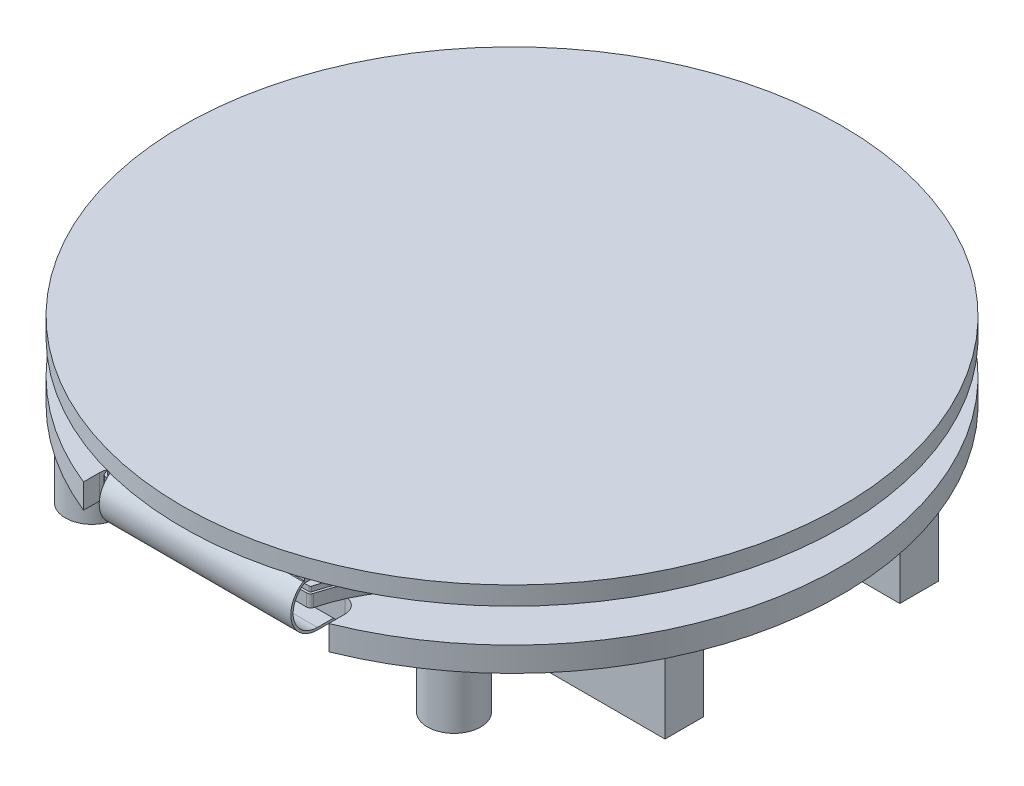
SolidWorks part; units mm, degrees
ref_plane "Front Plane" through (0, 0, 0) normal (0, 0, 1) x (1, 0, 0)
ref_plane "Top Plane" through (0, 0, 0) normal (0, 1, 0) x (1, 0, 0)
ref_plane "Right Plane" through (0, 0, 0) normal (1, 0, 0) x (0, 0, -1)
sketch "Sketch1" plane through (0, 0, 0) normal (0, 1, 0) x (1, 0, 0)
  line L0 (0, 17.75) -> (0, -19.95) construction
  line L1 (-6.75, -19.95) -> (6.75, -19.95)
  circle A0 centre (0, 0) radius 17.75
  arc A1 (-6.75, -19.95) -> (-10.0986, -14.5973) centre (-16.4685, -22.306) ccw
  arc A2 (6.75, -19.95) -> (10.0986, -14.5973) centre (16.4685, -22.306) cw
  point P8 (0, -19.95)
  dimension "D1" = 35.5
  dimension "D4" = 10
  dimension "D2" = 37.7
  dimension "D3" = 13.5
extrude "Boss-Extrude1" add sketch "Sketch1" along normal blind 0.8 contours A0 L0 L1 A2 | L0 A0 A1 L1 | L0 A0 | A0 L0 region at (7.5333, 0, 0) region at (-7.5333, 0, 0) region at (4.3011, 0, 18.3367) region at (-4.3011, 0, 18.3367)
fillet "Fillet1" radius 0.25 2 edges at (6.75, 0.4, 19.95) (-6.75, 0.4, 19.95)
sketch "Sketch2" plane through (0, 0.8, 0) normal (0, 1, 0) x (1, 0, 0)
  line L1 (-6.5553, -19.8) -> (6.5553, -19.8)
  line L3 (-6.5553, -19.95) -> (6.5553, -19.95)
  line L4 (-6.5553, -19.95) -> (6.5553, -19.95) construction
  arc A3 (6.5553, -19.8) -> (6.652, -19.7254) centre (6.5553, -19.7) ccw
  arc A4 (10.0081, -14.4775) -> (6.652, -19.7254) centre (16.4685, -22.306) ccw
  arc A5 (10.0081, -14.4775) -> (-10.0081, -14.4775) centre (0, 0) ccw
  arc A9 (-6.652, -19.7254) -> (-10.0081, -14.4775) centre (-16.4685, -22.306) ccw
  arc A10 (-6.652, -19.7254) -> (-6.5553, -19.8) centre (-6.5553, -19.7) ccw
  arc A11 (6.5553, -19.95) -> (6.7971, -19.7636) centre (6.5553, -19.7) ccw
  arc A12 (10.0986, -14.5973) -> (6.7971, -19.7636) centre (16.4685, -22.306) ccw
  arc A13 (10.0986, -14.5973) -> (-10.0986, -14.5973) centre (0, 0) ccw
  arc A14 (-6.7971, -19.7636) -> (-10.0986, -14.5973) centre (-16.4685, -22.306) ccw
  arc A15 (-6.7971, -19.7636) -> (-6.5553, -19.95) centre (-6.5553, -19.7) ccw
  arc A16 (6.5553, -19.95) -> (6.7971, -19.7636) centre (6.5553, -19.7) ccw construction
  arc A17 (10.0986, -14.5973) -> (6.7971, -19.7636) centre (16.4685, -22.306) ccw construction
  arc A18 (10.0986, -14.5973) -> (-10.0986, -14.5973) centre (0, 0) ccw construction
  arc A19 (-6.7971, -19.7636) -> (-10.0986, -14.5973) centre (-16.4685, -22.306) ccw construction
  arc A20 (-6.7971, -19.7636) -> (-6.5553, -19.95) centre (-6.5553, -19.7) ccw construction
  dimension "D1" = 0
  dimension "D2" = 0.15
extrude "Boss-Extrude2" add sketch "Sketch2" along normal blind 0.82
sketch "Sketch4" plane through (0, 1.62, 0) normal (0, 1, 0) x (1, 0, 0)
  line L0 (0, 0) -> (0, -19.95) construction
  line L1 (-6.5553, -19.95) -> (6.5553, -19.95) construction
  line L2 (10, -16.95) -> (-10, -16.95)
  line L5 (-10, -16.95) -> (-10, -19.95)
  line L6 (-10, -19.95) -> (10, -19.95)
  line L7 (10, -16.95) -> (10, -19.95)
  point P8 (0, -16.95)
  dimension "D1" = 3
  dimension "D2" = 20
  dimension "D3" = 3
extrude "Cut-Extrude1" cut sketch "Sketch4" against normal blind 0.5
sketch "Sketch5" plane through (0, 1.12, 0) normal (0, 1, 0) x (1, 0, 0)
  line L0 (0, -19.95) -> (0, -16.95) construction
  line L1 (-6.5553, -19.95) -> (6.5553, -19.95) construction
  line L2 (7.8467, -16.95) -> (-7.8467, -16.95) construction
  line L3 (7.8467, -16.95) -> (-7.8467, -16.95) construction
  line L4 (-5.45, -17.55) -> (5.45, -17.55)
  line L5 (-5.45, -17.55) -> (-5.45, -18.35)
  line L6 (-5.45, -18.35) -> (5.45, -18.35)
  line L7 (5.45, -17.55) -> (5.45, -18.35)
  line L8 (-5.45, -17.55) -> (5.45, -18.35) construction
  line L9 (-5.45, -18.35) -> (5.45, -17.55) construction
  line L10 (-6.25, -19) -> (6.25, -19)
  line L11 (-6.25, -19) -> (-6.25, -19.8)
  line L12 (-6.25, -19.8) -> (6.25, -19.8)
  line L13 (6.25, -19) -> (6.25, -19.8)
  line L14 (-6.25, -19) -> (6.25, -19.8) construction
  line L15 (-6.25, -19.8) -> (6.25, -19) construction
  line L16 (-6.5553, -19.8) -> (6.5553, -19.8) construction
  point P6 (0, -17.95)
  point P11 (0, -19.4)
  dimension "D1" = 0.8
  dimension "D2" = 0.8
  dimension "D3" = 0.6
  dimension "D4" = 12.5
  dimension "D5" = 10.9
extrude "Boss-Extrude3" add sketch "Sketch5" along normal blind 0.3
sketch "Sketch6" plane through (0, 0, 0) normal (0, -1, 0) x (1, 0, 0)
  line L0 (-17.2934, -4) -> (17.2934, -4) construction
  arc A0 (-10.0986, 14.5973) -> (10.0986, 14.5973) centre (0, 0) ccw construction
  text T0 "LCD GC9A01" font "Arial" height 2
  dimension "D1" = 4
extrude "Cut-Extrude2" cut sketch "Sketch6" against normal blind 0.001
sketch "Sketch8" plane through (0, 0, 0) normal (1, 0, 0) x (0, 0, -1)
  line L0 (-18.95, -1.8) -> (-10.65, -1.8)
  line L1 (-19.7636, 0) -> (-14.5973, 0) construction
  line L2 (-19.95, 0) -> (-19.95, 0.8) construction
  line L3 (-18.95, -1.95) -> (-10.65, -1.95)
  line L4 (-19.8805, 1.2466) -> (-19.8, 1.2466)
  line L6 (-19.8, 1.42) -> (-19.8, 1.12) construction
  line L7 (-19.8, 1.2466) -> (-19.8, 1.12)
  line L8 (-10.65, -1.8) -> (-10.65, -1.95)
  arc A0 (-19.8, 1.12) -> (-18.95, -1.8) centre (-18.95, -0.2163) ccw
  arc A1 (-19.8805, 1.2466) -> (-18.95, -1.95) centre (-18.95, -0.2163) ccw
  dimension "D1" = 1.8
  dimension "D2" = 9.3
  dimension "D4" = 1
  dimension "D5" = 0.15
extrude "Boss-Extrude4" add sketch "Sketch8" along normal mid plane 12.5 separate body
sketch "Sketch9" plane through (0, -1.95, 0) normal (0, -1, 0) x (1, 0, 0)
  line L0 (-5.15, 19.95) -> (-5.15, 14.45) construction
  line L1 (-6.5553, 19.95) -> (6.5553, 19.95) construction
  line L2 (-6.25, 18.95) -> (-6.25, 10.65) construction
  line L3 (0, 19.95) -> (0, 10.65) construction
  line L4 (6.25, 10.65) -> (-6.25, 10.65) construction
  circle A0 centre (-5.15, 14.45) radius 0.5
  circle A1 centre (5.15, 14.45) radius 0.5
  dimension "D3" = 1
  dimension "D1" = 5.5
  dimension "D2" = 1.1
extrude "Cut-Extrude3" cut sketch "Sketch9" against normal blind 0.2
sketch "Sketch10" plane through (0, -1.95, 0) normal (0, -1, 0) x (1, 0, 0)
  line L0 (-6.25, 18.95) -> (-6.25, 10.65) construction
  line L1 (6.25, 10.65) -> (5.15, 10.65)
  line L2 (6.25, 10.65) -> (6.25, 14.15)
  line L3 (6.25, 14.15) -> (6.15, 14.15)
  line L4 (5.15, 10.65) -> (5.15, 13.15)
  arc A0 (6.15, 14.15) -> (5.15, 13.15) centre (6.15, 13.15) ccw
  dimension "D3" = 1
  dimension "D1" = 11.4
  dimension "D2" = 3.5
extrude "Cut-Extrude4" cut sketch "Sketch10" against normal blind 0.2
fillet "Fillet2" radius 0.5 1 edges at (6.25, -1.875, 14.15)
fillet "Fillet3" radius 0.5 2 edges at (5.15, -1.875, 10.65) (-6.25, -1.875, 10.65)
sketch "Sketch11" plane through (0, -1.95, 0) normal (0, -1, 0) x (1, 0, 0)
  line L0 (4.65, 10.65) -> (-5.75, 10.65) construction
  line L1 (-4.65, 10.65) -> (-4.15, 10.65)
  line L2 (-4.65, 10.65) -> (-4.65, 12.65)
  line L3 (-4.65, 12.65) -> (-4.15, 12.65)
  line L4 (-4.15, 10.65) -> (-4.15, 12.65)
  line L5 (-6.25, 18.95) -> (-6.25, 11.15) construction
  line L6 (-3.95, 10.65) -> (-3.45, 10.65)
  line L7 (-3.95, 10.65) -> (-3.95, 12.65)
  line L8 (-3.95, 12.65) -> (-3.45, 12.65)
  line L9 (-3.45, 10.65) -> (-3.45, 12.65)
  line L10 (-3.25, 10.65) -> (-2.75, 10.65)
  line L11 (-3.25, 10.65) -> (-3.25, 12.65)
  line L12 (-3.25, 12.65) -> (-2.75, 12.65)
  line L13 (-2.75, 10.65) -> (-2.75, 12.65)
  line L14 (-2.55, 10.65) -> (-2.05, 10.65)
  line L15 (-2.55, 10.65) -> (-2.55, 12.65)
  line L16 (-2.55, 12.65) -> (-2.05, 12.65)
  line L17 (-2.05, 10.65) -> (-2.05, 12.65)
  line L18 (-1.85, 10.65) -> (-1.35, 10.65)
  line L19 (-1.85, 10.65) -> (-1.85, 12.65)
  line L20 (-1.85, 12.65) -> (-1.35, 12.65)
  line L21 (-1.35, 10.65) -> (-1.35, 12.65)
  line L22 (-1.15, 10.65) -> (-0.65, 10.65)
  line L23 (-1.15, 10.65) -> (-1.15, 12.65)
  line L24 (-1.15, 12.65) -> (-0.65, 12.65)
  line L25 (-0.65, 10.65) -> (-0.65, 12.65)
  line L26 (-0.45, 10.65) -> (0.05, 10.65)
  line L27 (-0.45, 10.65) -> (-0.45, 12.65)
  line L28 (-0.45, 12.65) -> (0.05, 12.65)
  line L29 (0.05, 10.65) -> (0.05, 12.65)
  line L30 (0.25, 10.65) -> (0.75, 10.65)
  line L31 (0.25, 10.65) -> (0.25, 12.65)
  line L32 (0.25, 12.65) -> (0.75, 12.65)
  line L33 (0.75, 10.65) -> (0.75, 12.65)
  line L34 (0.95, 10.65) -> (1.45, 10.65)
  line L35 (0.95, 10.65) -> (0.95, 12.65)
  line L36 (0.95, 12.65) -> (1.45, 12.65)
  line L37 (1.45, 10.65) -> (1.45, 12.65)
  line L38 (1.65, 10.65) -> (2.15, 10.65)
  line L39 (1.65, 10.65) -> (1.65, 12.65)
  line L40 (1.65, 12.65) -> (2.15, 12.65)
  line L41 (2.15, 10.65) -> (2.15, 12.65)
  line L42 (2.35, 10.65) -> (2.85, 10.65)
  line L43 (2.35, 10.65) -> (2.35, 12.65)
  line L44 (2.35, 12.65) -> (2.85, 12.65)
  line L45 (2.85, 10.65) -> (2.85, 12.65)
  line L46 (3.05, 10.65) -> (3.55, 10.65)
  line L47 (3.05, 10.65) -> (3.05, 12.65)
  line L48 (3.05, 12.65) -> (3.55, 12.65)
  line L49 (3.55, 10.65) -> (3.55, 12.65)
  line L50 (5.15, 13.15) -> (5.15, 11.15) construction
  dimension "D1" = 0.5
  dimension "D2" = 2
  dimension "D3" = 1.6
  dimension "D5" = 1.6
  dimension "D4" = 12
extrude "Cut-Extrude5" cut sketch "Sketch11" against normal blind 0.01
sketch "Esquisse1" plane through (0, 0, 0) normal (0, 1, 0) x (1, 0, 0)
  line L1 (-8, -25.1) -> (8, -25.1)
  line L2 (-8, -25.1) -> (-8, -18.9)
  line L3 (-7, -17.9) -> (7, -17.9)
  line L4 (8, -25.1) -> (8, -18.9)
  line L5 (-8, -25.1) -> (8, -17.9) construction
  line L6 (-8, -17.9) -> (8, -25.1) construction
  circle A0 centre (0, 0) radius 21.5
  arc A1 (-8, -18.9) -> (-7, -17.9) centre (-7, -18.9) cw
  arc A2 (7, -17.9) -> (8, -18.9) centre (7, -18.9) cw
  point P3 (0, -21.5)
  dimension "D1" = 43
  dimension "D4" = 1
  dimension "D2" = 16
  dimension "D3" = 3.6
extrude "Boss.-Extru.1" add sketch "Esquisse1" against normal blind 1.6 from offset 0.2 separate body contours L3 A2 L4 A0 L2 A1 region at (0, 0, -0.6815) offset against normal yes
sketch "Esquisse2" plane through (0, 0, 0) normal (0, 1, 0) x (1, 0, 0)
  circle A0 centre (0, 0) radius 21.5
  arc A1 (8, -19.9562) -> (-8, -19.9562) centre (0, 0) ccw construction
extrude "Boss.-Extru.2" add sketch "Esquisse2" along normal blind 1.1 from offset 2.1 separate body
sketch "Esquisse3" plane through (0, 2.1, 0) normal (0, -1, 0) x (1, 0, 0)
  circle A0 centre (0, 0) radius 21.5 construction
  circle A1 centre (0, 0) radius 21.5
  circle A2 centre (0, 0) radius 16.5
  dimension "D1" = 5
extrude "Boss.-Extru.3" add sketch "Esquisse3" along normal blind 0.1
sketch "Esquisse4" plane through (0, -1.8, 0) normal (0, -1, 0) x (1, 0, 0)
  line L0 (0, -19.46) -> (11.811, 15.5937) construction
  line L1 (11.811, 15.5937) -> (-11.811, 15.5937) construction
  line L2 (-11.811, 15.5937) -> (0, -19.46) construction
  line L3 (0, -19.46) -> (0, 15.5937) construction
  circle A0 centre (0, -19.46) radius 0.8
  circle A1 centre (11.811, 15.5937) radius 0.8
  circle A2 centre (-11.811, 15.5937) radius 0.8
  circle A3 centre (0, -19.46) radius 1.735
  circle A4 centre (11.811, 15.5937) radius 1.735
  circle A5 centre (-11.811, 15.5937) radius 1.735
  dimension "D3" = 3.47
  dimension "D4" = 1.6
  dimension "D1" = 19.46
  dimension "D2" = 23.622
  dimension "D5" = 36.99
extrude "Boss.-Extru.4" add sketch "Esquisse4" along normal blind 3.66 separate body
sketch "Esquisse5" plane through (0, -1.8, 0) normal (0, -1, 0) x (1, 0, 0)
  line L0 (0.55, 7.66) -> (2.105, 7.66) construction
  line L1 (18.9, 8.92) -> (0.55, 8.92)
  line L2 (18.9, 8.92) -> (18.9, 6.4)
  line L3 (18.9, 6.4) -> (0.55, 6.4)
  line L4 (0.55, 8.92) -> (0.55, 6.4)
  line L5 (2.105, 7.66) -> (4.645, 7.66) construction
  line L6 (4.645, 7.66) -> (7.185, 7.66) construction
  line L7 (7.185, 7.66) -> (9.725, 7.66) construction
  line L8 (9.725, 7.66) -> (12.265, 7.66) construction
  line L9 (12.265, 7.66) -> (14.805, 7.66) construction
  line L10 (14.805, 7.66) -> (17.345, 7.66) construction
  line L11 (17.345, 7.66) -> (18.9, 7.66) construction
  line L12 (2.8325, 0) -> (-2.8325, 0) construction
  line L13 (1.755, 8.01) -> (2.455, 8.01)
  line L14 (1.755, 8.01) -> (1.755, 7.31)
  line L15 (1.755, 7.31) -> (2.455, 7.31)
  line L16 (2.455, 8.01) -> (2.455, 7.31)
  line L17 (1.755, 8.01) -> (2.455, 7.31) construction
  line L18 (1.755, 7.31) -> (2.455, 8.01) construction
  line L19 (4.295, 8.01) -> (4.995, 8.01)
  line L20 (4.295, 8.01) -> (4.295, 7.31)
  line L21 (4.295, 7.31) -> (4.995, 7.31)
  line L22 (4.995, 8.01) -> (4.995, 7.31)
  line L23 (4.295, 8.01) -> (4.995, 7.31) construction
  line L24 (4.295, 7.31) -> (4.995, 8.01) construction
  line L25 (6.835, 8.01) -> (7.535, 8.01)
  line L26 (6.835, 8.01) -> (6.835, 7.31)
  line L27 (6.835, 7.31) -> (7.535, 7.31)
  line L28 (7.535, 8.01) -> (7.535, 7.31)
  line L29 (6.835, 8.01) -> (7.535, 7.31) construction
  line L30 (6.835, 7.31) -> (7.535, 8.01) construction
  line L31 (9.375, 8.01) -> (10.075, 8.01)
  line L32 (9.375, 8.01) -> (9.375, 7.31)
  line L33 (9.375, 7.31) -> (10.075, 7.31)
  line L34 (10.075, 8.01) -> (10.075, 7.31)
  line L35 (9.375, 8.01) -> (10.075, 7.31) construction
  line L36 (9.375, 7.31) -> (10.075, 8.01) construction
  line L37 (11.915, 8.01) -> (12.615, 8.01)
  line L38 (11.915, 8.01) -> (11.915, 7.31)
  line L39 (11.915, 7.31) -> (12.615, 7.31)
  line L40 (12.615, 8.01) -> (12.615, 7.31)
  line L41 (11.915, 8.01) -> (12.615, 7.31) construction
  line L42 (11.915, 7.31) -> (12.615, 8.01) construction
  line L43 (14.455, 8.01) -> (15.155, 8.01)
  line L44 (14.455, 8.01) -> (14.455, 7.31)
  line L45 (14.455, 7.31) -> (15.155, 7.31)
  line L46 (15.155, 8.01) -> (15.155, 7.31)
  line L47 (14.455, 8.01) -> (15.155, 7.31) construction
  line L48 (14.455, 7.31) -> (15.155, 8.01) construction
  line L49 (16.995, 8.01) -> (17.695, 8.01)
  line L50 (16.995, 8.01) -> (16.995, 7.31)
  line L51 (16.995, 7.31) -> (17.695, 7.31)
  line L52 (17.695, 8.01) -> (17.695, 7.31)
  line L53 (16.995, 8.01) -> (17.695, 7.31) construction
  line L54 (16.995, 7.31) -> (17.695, 8.01) construction
  line L55 (16.995, -7.31) -> (17.695, -8.01) construction
  line L56 (16.995, -8.01) -> (17.695, -7.31) construction
  line L57 (14.455, -7.31) -> (15.155, -8.01) construction
  line L58 (14.455, -8.01) -> (15.155, -7.31) construction
  line L59 (11.915, -7.31) -> (12.615, -8.01) construction
  line L60 (11.915, -8.01) -> (12.615, -7.31) construction
  line L61 (9.375, -7.31) -> (10.075, -8.01) construction
  line L62 (9.375, -8.01) -> (10.075, -7.31) construction
  line L63 (6.835, -7.31) -> (7.535, -8.01) construction
  line L64 (6.835, -8.01) -> (7.535, -7.31) construction
  line L65 (4.295, -7.31) -> (4.995, -8.01) construction
  line L66 (4.295, -8.01) -> (4.995, -7.31) construction
  line L67 (1.755, -7.31) -> (2.455, -8.01) construction
  line L68 (1.755, -8.01) -> (2.455, -7.31) construction
  line L69 (17.345, -7.66) -> (18.9, -7.66) construction
  line L70 (14.805, -7.66) -> (17.345, -7.66) construction
  line L71 (12.265, -7.66) -> (14.805, -7.66) construction
  line L72 (9.725, -7.66) -> (12.265, -7.66) construction
  line L73 (7.185, -7.66) -> (9.725, -7.66) construction
  line L74 (4.645, -7.66) -> (7.185, -7.66) construction
  line L75 (2.105, -7.66) -> (4.645, -7.66) construction
  line L76 (0.55, -7.66) -> (2.105, -7.66) construction
  line L77 (17.695, -8.01) -> (17.695, -7.31)
  line L78 (16.995, -7.31) -> (17.695, -7.31)
  line L79 (16.995, -8.01) -> (16.995, -7.31)
  line L80 (16.995, -8.01) -> (17.695, -8.01)
  line L81 (15.155, -8.01) -> (15.155, -7.31)
  line L82 (14.455, -7.31) -> (15.155, -7.31)
  line L83 (14.455, -8.01) -> (14.455, -7.31)
  line L84 (14.455, -8.01) -> (15.155, -8.01)
  line L85 (12.615, -8.01) -> (12.615, -7.31)
  line L86 (11.915, -7.31) -> (12.615, -7.31)
  line L87 (11.915, -8.01) -> (11.915, -7.31)
  line L88 (11.915, -8.01) -> (12.615, -8.01)
  line L89 (10.075, -8.01) -> (10.075, -7.31)
  line L90 (9.375, -7.31) -> (10.075, -7.31)
  line L91 (9.375, -8.01) -> (9.375, -7.31)
  line L92 (9.375, -8.01) -> (10.075, -8.01)
  line L93 (7.535, -8.01) -> (7.535, -7.31)
  line L94 (6.835, -7.31) -> (7.535, -7.31)
  line L95 (6.835, -8.01) -> (6.835, -7.31)
  line L96 (6.835, -8.01) -> (7.535, -8.01)
  line L97 (4.995, -8.01) -> (4.995, -7.31)
  line L98 (4.295, -7.31) -> (4.995, -7.31)
  line L99 (4.295, -8.01) -> (4.295, -7.31)
  line L100 (4.295, -8.01) -> (4.995, -8.01)
  line L101 (2.455, -8.01) -> (2.455, -7.31)
  line L102 (1.755, -7.31) -> (2.455, -7.31)
  line L103 (1.755, -8.01) -> (1.755, -7.31)
  line L104 (1.755, -8.01) -> (2.455, -8.01)
  line L105 (0.55, -8.92) -> (0.55, -6.4)
  line L106 (18.9, -6.4) -> (0.55, -6.4)
  line L107 (18.9, -8.92) -> (18.9, -6.4)
  line L108 (18.9, -8.92) -> (0.55, -8.92)
  arc A0 (-8, 19.9562) -> (8, 19.9562) centre (0, 0) ccw construction
  dimension "D1" = 18.35
  dimension "D2" = 2.52
  dimension "D3" = 2.54
  dimension "D4" = 0.7
  dimension "D5" = 6.4
  dimension "D6" = 2.6
extrude "Boss.-Extru.5" add sketch "Esquisse5" along normal blind 5 separate body
sketch "Esquisse6" plane through (0, -1.8, 0) normal (0, -1, 0) x (1, 0, 0)
  line L0 (-16.9547, 12.0004) -> (-14.4383, 10.7725)
  line L1 (-16.9547, 12.0004) -> (-19.8928, 5.979)
  line L2 (-14.4383, 10.7725) -> (-17.3764, 4.7511)
  line L3 (-19.8928, 5.979) -> (-17.3764, 4.7511)
  line L4 (-18.4238, 8.9897) -> (0, 0) construction
  arc A0 (-8, 19.9562) -> (8, 19.9562) centre (0, 0) ccw construction
  circle A1 centre (-11.811, 15.5937) radius 1.735 construction
  point P7 (-15.9074, 7.7618)
  dimension "D3" = 1
  dimension "D4" = 3.75
  dimension "D1" = 2.8
  dimension "D2" = 6.7
extrude "Boss.-Extru.6" add sketch "Esquisse6" along normal blind 1.44 separate body
sketch "Esquisse7" plane through (-18.4238, 0, 8.9897) normal (-0.8987, 0, 0.4385) x (0.4385, 0, 0.8987)
  line L1 (1.35, -1.8) -> (0.05, -1.8)
  line L2 (1.35, -1.8) -> (1.35, -2.8)
  line L3 (1.35, -2.8) -> (0.05, -2.8)
  line L4 (0.05, -1.8) -> (0.05, -2.8)
  line L5 (3.35, -1.8) -> (-3.35, -1.8) construction
  line L6 (3.35, -3.24) -> (3.35, -1.8) construction
  dimension "D1" = 1.3
  dimension "D2" = 1
  dimension "D3" = 2
extrude "Boss.-Extru.7" add sketch "Esquisse7" along normal blind 1.4
sketch "Esquisse8" plane through (0, -1.8, 0) normal (0, -1, 0) x (1, 0, 0)
  line L1 (-10.3, 5.75) -> (-5.3, 5.75)
  line L2 (-10.3, 5.75) -> (-10.3, -5.75)
  line L3 (-10.3, -5.75) -> (-5.3, -5.75)
  line L4 (-5.3, 5.75) -> (-5.3, -5.75)
  line L5 (-10.3, 5.75) -> (-5.3, -5.75) construction
  line L6 (-10.3, -5.75) -> (-5.3, 5.75) construction
  arc A0 (-8, 19.9562) -> (8, 19.9562) centre (0, 0) ccw construction
  point P0 (-7.8, 0)
  dimension "D3" = 11.2
  dimension "D1" = 11.5
  dimension "D2" = 5
extrude "Boss.-Extru.8" add sketch "Esquisse8" along normal blind 3 separate body
sketch "Esquisse9" plane through (-10.3, 0, 0) normal (-1, 0, 0) x (0, 0, 1)
  line L0 (5.75, -4.8) -> (-5.75, -4.8) construction
  line L1 (5.35, -4.6) -> (-5.35, -4.6)
  line L2 (5.35, -4.6) -> (5.35, -3.4)
  line L3 (5.35, -3.4) -> (-5.35, -3.4)
  line L4 (-5.35, -4.6) -> (-5.35, -3.4)
  line L5 (5.75, -4.8) -> (5.75, -1.8) construction
  line L6 (-5.75, -4.8) -> (-5.75, -1.8) construction
  dimension "D1" = 0.2
  dimension "D2" = 0.4
  dimension "D3" = 0.4
  dimension "D4" = 1.2
extrude "Enlèv. mat.-Extru.1" cut sketch "Esquisse9" against normal blind 4
sketch "Esquisse10" plane through (0, -1.8, 0) normal (0, -1, 0) x (1, 0, 0)
  line L0 (-11.1243, -14.0492) -> (-6.2447, -16.7969)
  line L1 (-8.6845, -15.423) -> (0, 0) construction
  circle A0 centre (-6.652, -11.8135) radius 5
  arc A1 (-8, 19.9562) -> (8, 19.9562) centre (0, 0) ccw construction
  circle A2 centre (0, -19.46) radius 1.735 construction
  dimension "D1" = 10
  dimension "D4" = 3.4
  dimension "D2" = 5.6
  dimension "D3" = 3.8
extrude "Boss.-Extru.9" add sketch "Esquisse10" along normal blind 0.2 from offset 2.6 separate body contours L0 L1 A0 | L1 L0 A0 region at (-8.4456, -1.8, -10.5804) region at (-4.6675, -1.8, -12.7078)
sketch "Esquisse11" plane through (0, -4.6, 0) normal (0, -1, 0) x (1, 0, 0)
  line L0 (-5.1192, -7.0532) -> (-3.3764, -8.0345)
  line L1 (-5.1192, -7.0532) -> (-5.021, -6.8789)
  line L2 (-3.3764, -8.0345) -> (-3.2783, -7.8602)
  line L3 (-5.021, -6.8789) -> (-3.2783, -7.8602)
  line L4 (-5.1192, -7.0532) -> (-3.2783, -7.8602) construction
  line L5 (-3.3764, -8.0345) -> (-5.021, -6.8789) construction
  line L6 (-11.5865, -10.1825) -> (-10.6053, -8.4398)
  line L7 (-11.5865, -10.1825) -> (-11.4123, -10.2807)
  line L8 (-10.6053, -8.4398) -> (-10.431, -8.5379)
  line L9 (-11.4123, -10.2807) -> (-10.431, -8.5379)
  line L10 (-11.5865, -10.1825) -> (-10.431, -8.5379) construction
  line L11 (-10.6053, -8.4398) -> (-11.4123, -10.2807) construction
  line L12 (-2.873, -15.089) -> (-1.8917, -13.3463)
  line L13 (-2.873, -15.089) -> (-2.6987, -15.1871)
  line L14 (-1.8917, -13.3463) -> (-1.7174, -13.4444)
  line L15 (-2.6987, -15.1871) -> (-1.7174, -13.4444)
  line L16 (-2.873, -15.089) -> (-1.7174, -13.4444) construction
  line L17 (-1.8917, -13.3463) -> (-2.6987, -15.1871) construction
  line L19 (0, 0) -> (-4.1987, -7.4567) construction
  line L21 (-11.0088, -9.3602) -> (-2.2952, -14.2667) construction
  arc A0 (-6.2447, -16.7969) -> (-11.1243, -14.0492) centre (-6.652, -11.8135) ccw construction
  point P1 (-4.1987, -7.4567)
  point P2 (-11.0088, -9.3602)
  point P3 (-2.2952, -14.2667)
  point P27 (-6.652, -11.8135)
  dimension "D2" = 0.2
  dimension "D3" = 2
extrude "Boss.-Extru.10" add sketch "Esquisse11" against normal up to surface (2.8 mm away) up to face at (0, -1.8, 11.9403)
sketch "Esquisse12" plane through (0, -1.8, 0) normal (0, -1, 0) x (1, 0, 0)
  line L1 (-3.7, 2.65) -> (0.3, 2.65)
  line L2 (-3.7, 2.65) -> (-3.7, -2.65)
  line L3 (-3.7, -2.65) -> (0.3, -2.65)
  line L4 (0.3, 2.65) -> (0.3, -2.65)
  line L5 (-3.7, 2.65) -> (0.3, -2.65) construction
  line L6 (-3.7, -2.65) -> (0.3, 2.65) construction
  arc A0 (-8, 19.9562) -> (8, 19.9562) centre (0, 0) ccw construction
  point P0 (-1.7, 0)
  dimension "D3" = 21.8
  dimension "D1" = 5.3
  dimension "D2" = 4
extrude "Boss.-Extru.11" add sketch "Esquisse12" along normal blind 2.6 separate body
sketch "Esquisse13" plane through (0, -4.4, 0) normal (0, -1, 0) x (1, 0, 0)
  line L0 (-1.7, 2.65) -> (-1.7, 0) construction
  line L1 (-2.6, 0.6) -> (-1.8, 0.6)
  line L2 (-2.6, 0.6) -> (-2.6, -0.6)
  line L3 (-2.6, -0.6) -> (-1.8, -0.6)
  line L4 (-1.8, 0.6) -> (-1.8, -0.6)
  line L5 (-2.6, 0.6) -> (-1.8, -0.6) construction
  line L6 (-2.6, -0.6) -> (-1.8, 0.6) construction
  line L7 (-1.6, 0.6) -> (-0.8, 0.6)
  line L8 (-1.6, 0.6) -> (-1.6, -0.6)
  line L9 (-1.6, -0.6) -> (-0.8, -0.6)
  line L10 (-0.8, 0.6) -> (-0.8, -0.6)
  line L11 (-1.6, 0.6) -> (-0.8, -0.6) construction
  line L12 (-1.6, -0.6) -> (-0.8, 0.6) construction
  line L13 (0.3, 2.65) -> (-3.7, 2.65) construction
  line L14 (-2.2, 0) -> (-1.2, 0) construction
  point P0 (-2.2, 0)
  point P5 (-1.2, 0)
  dimension "D1" = 0.2
  dimension "D2" = 0.8
  dimension "D3" = 1.2
extrude "Enlèv. mat.-Extru.2" cut sketch "Esquisse13" against normal blind 1
chamfer "Chanfrein1" distance 0.8 angle 45 4 edges at (-1.2, -4.4, -0.6) (-2.2, -4.4, -0.6) (-1.2, -4.4, 0.6) (-2.2, -4.4, 0.6)
sketch "Esquisse14" plane through (0, -3.4, 0) normal (0, -1, 0) x (1, 0, 0)
  line L0 (-1.8, 0.4) -> (-2.6, 0.4) construction
  line L1 (-2.5, 0.3) -> (-1.9, 0.3)
  line L2 (-2.5, 0.3) -> (-2.5, -0.3)
  line L3 (-2.5, -0.3) -> (-1.9, -0.3)
  line L4 (-1.9, 0.3) -> (-1.9, -0.3)
  line L5 (-2.5, 0.3) -> (-1.9, -0.3) construction
  line L6 (-2.5, -0.3) -> (-1.9, 0.3) construction
  line L7 (-0.8, 0.4) -> (-1.6, 0.4) construction
  line L8 (-1.5, 0.3) -> (-0.9, 0.3)
  line L9 (-1.5, 0.3) -> (-1.5, -0.3)
  line L10 (-1.5, -0.3) -> (-0.9, -0.3)
  line L11 (-0.9, 0.3) -> (-0.9, -0.3)
  line L12 (-1.5, 0.3) -> (-0.9, -0.3) construction
  line L13 (-1.5, -0.3) -> (-0.9, 0.3) construction
  line L14 (-2.6, 0.6) -> (-2.6, -0.6) construction
  point P0 (-2.2, 0)
  point P7 (-2.2, 0.4)
  point P8 (-1.2, 0)
  point P15 (-1.2, 0.4)
  dimension "D1" = 0.1
  dimension "D2" = 0.1
extrude "Boss.-Extru.12" add sketch "Esquisse14" along normal up to surface (1 mm away) up to face at (-2.2, -4.4, 0)
